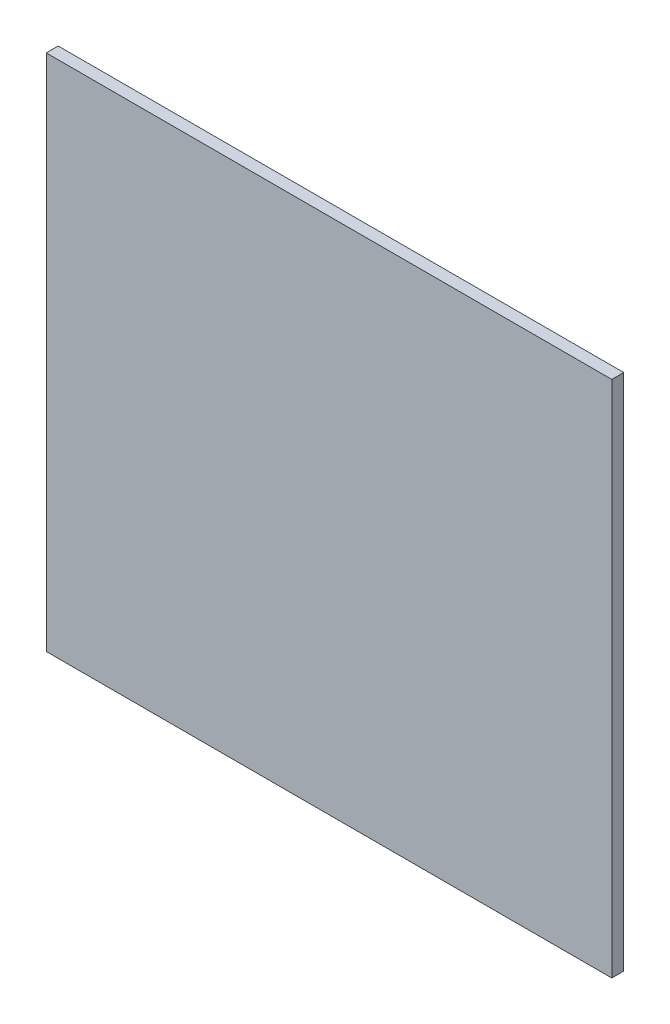
SolidWorks part; units mm, degrees
ref_plane "Front Plane" through (0, 0, 0) normal (0, 0, 1) x (1, 0, 0)
ref_plane "Top Plane" through (0, 0, 0) normal (0, 1, 0) x (1, 0, 0)
ref_plane "Right Plane" through (0, 0, 0) normal (1, 0, 0) x (0, 0, -1)
sketch "Sketch1" plane through (0, 0, 0) normal (0, 0, 1) x (1, 0, 0)
  line L1 (-150, 137.5) -> (150, 137.5)
  line L2 (-150, 137.5) -> (-150, -137.5)
  line L3 (-150, -137.5) -> (150, -137.5)
  line L4 (150, 137.5) -> (150, -137.5)
  line L5 (-150, 137.5) -> (150, -137.5) construction
  line L6 (-150, -137.5) -> (150, 137.5) construction
  point P0 (0, 0)
  dimension "D1" = 300
  dimension "D2" = 275
extrude "Boss-Extrude1" add sketch "Sketch1" along normal blind 6.35
